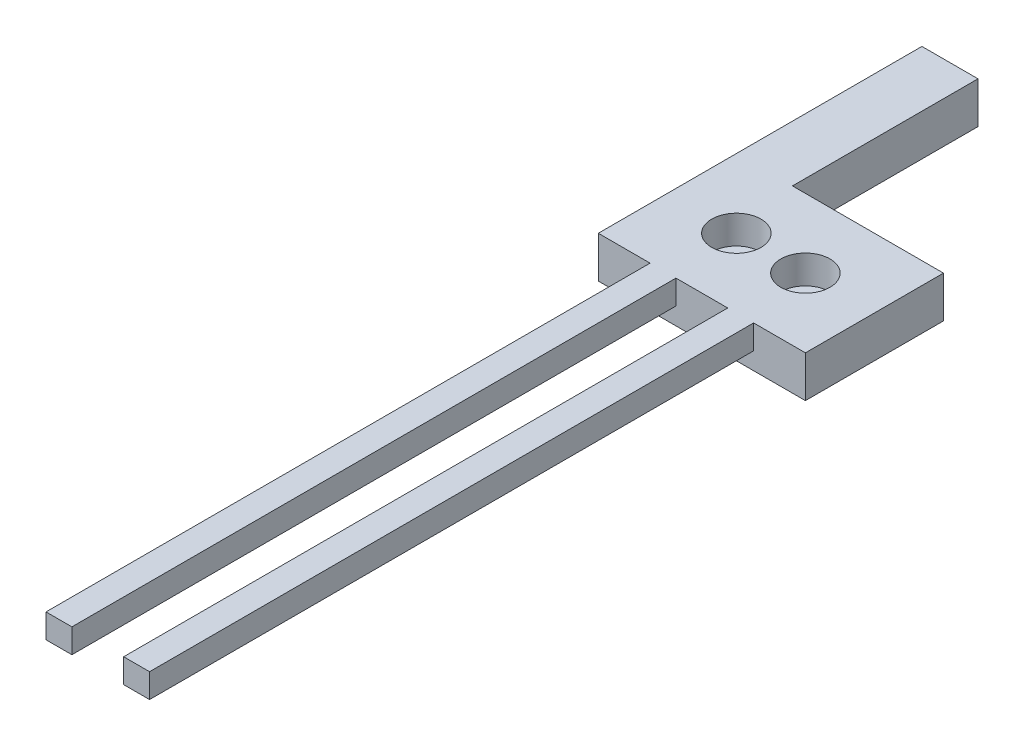
SolidWorks part; units mm, degrees
ref_plane "Front Plane" through (0, 0, 0) normal (0, 0, 1) x (1, 0, 0)
ref_plane "Top Plane" through (0, 0, 0) normal (0, 1, 0) x (1, 0, 0)
ref_plane "Right Plane" through (0, 0, 0) normal (1, 0, 0) x (0, 0, -1)
sketch "Sketch1" plane through (0, 0, 0) normal (0, -1, 0) x (1, 0, 0)
  line L0 (0, -8) -> (8, -8) construction
  line L1 (0, 0) -> (24, 0)
  line L2 (0, 0) -> (0, -16)
  line L3 (0, -16) -> (24, -16)
  line L4 (24, 0) -> (24, -16)
  line L5 (8, -8) -> (16, -8) construction
  line L6 (16, -8) -> (24, -8) construction
  circle A0 centre (8, -8) radius 1.65
  circle A1 centre (16, -8) radius 1.65
  dimension "D3" = 3.3
  dimension "D1" = 16
  dimension "D2" = 24
extrude "Boss-Extrude1" add sketch "Sketch1" along normal blind 4.8
sketch "Sketch2" plane through (0, 0, 0) normal (0, 0, 1) x (1, 0, 0)
  line L0 (24, 0) -> (0, 0) construction
  line L1 (6, 0) -> (9, 0)
  line L2 (6, 0) -> (6, -2.8)
  line L3 (6, -2.8) -> (9, -2.8)
  line L4 (9, 0) -> (9, -2.8)
  line L5 (0, 0) -> (6, 0) construction
  line L6 (15, 0) -> (18, 0)
  line L7 (15, 0) -> (15, -2.8)
  line L8 (15, -2.8) -> (18, -2.8)
  line L9 (18, 0) -> (18, -2.8)
  line L10 (9, 0) -> (15, 0) construction
  line L11 (18, 0) -> (24, 0) construction
  dimension "D1" = 2.8
  dimension "D2" = 3
  dimension "D3" = 3
extrude "Boss-Extrude2" add sketch "Sketch2" along normal blind 70
sketch "Sketch3" plane through (0, 0, 0) normal (0, 1, 0) x (1, 0, 0)
  circle A0 centre (8, 8) radius 2.85
  circle A1 centre (16, 8) radius 2.85
  dimension "D1" = 5.7
extrude "Cut-Extrude1" cut sketch "Sketch3" against normal blind 3.3
sketch "Sketch4" plane through (0, 0, 0) normal (0, 1, 0) x (1, 0, 0)
  line L0 (6.5, 37.5) -> (0, 37.5)
  line L1 (0, 37.5) -> (0, 16)
  line L2 (0, 16) -> (6.5, 16)
  line L3 (0, 16) -> (24, 16) construction
  line L4 (6.5, 16) -> (6.5, 37.5)
extrude "Boss-Extrude3" add sketch "Sketch4" against normal blind 4.8
